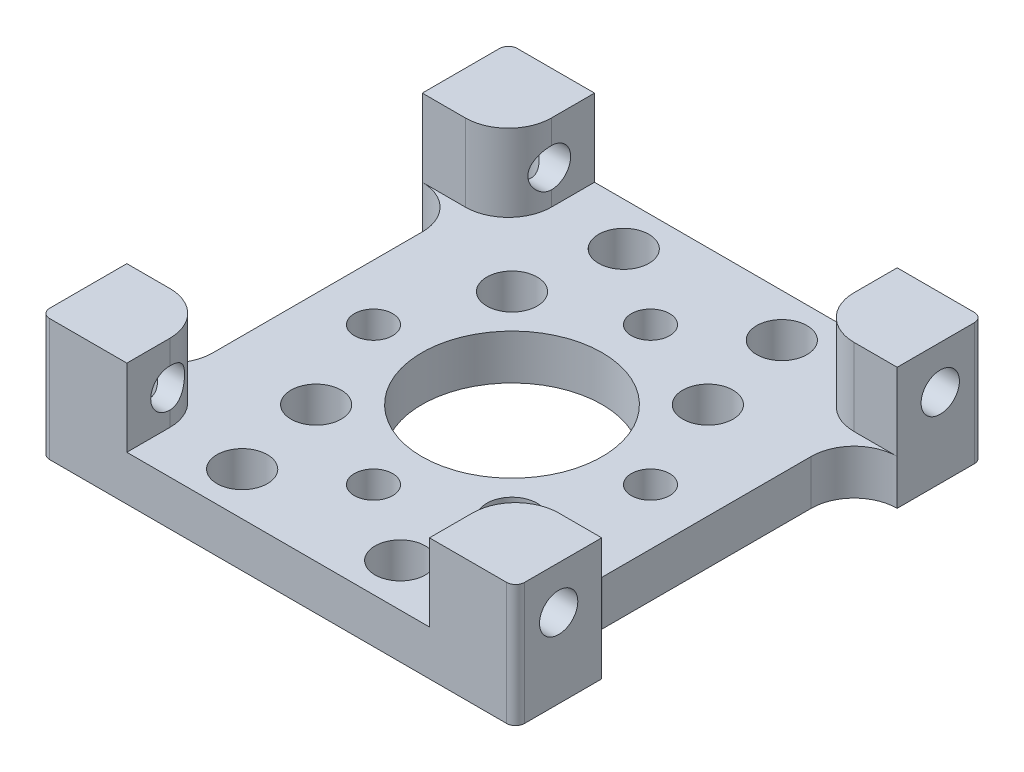
SolidWorks part; units mm, degrees
ref_plane "Front Plane" through (0, 0, 0) normal (0, 0, 1) x (1, 0, 0)
ref_plane "Top Plane" through (0, 0, 0) normal (0, 1, 0) x (1, 0, 0)
ref_plane "Right Plane" through (0, 0, 0) normal (1, 0, 0) x (0, 0, -1)
ref_plane "Plane1" through (0, 3.175, 0) normal (0, 1, 0) x (1, 0, 0)
sketch "Sketch1" plane through (0, 3.175, 0) normal (0, 1, 0) x (1, 0, 0)
  line L0 (16.764, -16.51) -> (16.764, 16.51)
  line L1 (16.764, 16.51) -> (-16.764, 16.51)
  line L2 (-16.764, 16.51) -> (-16.764, -16.51)
  line L3 (-16.764, -16.51) -> (16.764, -16.51)
extrude "Boss-Extrude1" add sketch "Sketch1" against normal blind 3.175
sketch "Sketch2" plane through (0, 0, 0) normal (0, -1, 0) x (1, 0, 0)
  line L0 (16.764, -10.4292) -> (16.764, 10.4292)
  line L1 (13.7287, 7.3889) -> (13.7287, -7.3889)
  arc A0 (16.764, 10.4292) -> (13.7287, 7.3889) centre (16.7691, 7.3889) ccw
  arc A1 (13.7287, -7.3889) -> (16.764, -10.4292) centre (16.7691, -7.3889) ccw
extrude "Cut-Extrude1" cut sketch "Sketch2" against normal through all
sketch "Sketch3" plane through (0, 0, 0) normal (0, -1, 0) x (1, 0, 0)
  line L0 (-16.764, 10.4292) -> (-16.764, -10.4292)
  line L1 (-13.7287, -7.3889) -> (-13.7287, 7.3889)
  arc A0 (-16.764, -10.4292) -> (-13.7287, -7.3889) centre (-16.7691, -7.3889) ccw
  arc A1 (-13.7287, 7.3889) -> (-16.764, 10.4292) centre (-16.7691, 7.3889) ccw
extrude "Cut-Extrude2" cut sketch "Sketch3" against normal through all
ref_plane "Plane2" through (0, 0, -16.51) normal (0, 0, -1) x (-1, 0, 0)
sketch "Sketch4" plane through (0, 0, -16.51) normal (0, 0, -1) x (-1, 0, 0)
  line L0 (10.6832, 3.175) -> (16.764, 3.175)
  line L1 (16.764, 3.175) -> (16.764, 8.6284)
  line L2 (16.764, 8.6284) -> (10.6832, 8.6284)
  line L3 (10.6832, 8.6284) -> (10.6832, 3.175)
extrude "Boss-Extrude2" add sketch "Sketch4" against normal blind 6.0808
sketch "Sketch5" plane through (0, 0, -16.51) normal (0, 0, -1) x (-1, 0, 0)
  line L0 (-16.764, 8.6284) -> (-16.764, 3.175)
  line L1 (-16.764, 3.175) -> (-10.6832, 3.175)
  line L2 (-10.6832, 3.175) -> (-10.6832, 8.6284)
  line L3 (-10.6832, 8.6284) -> (-16.764, 8.6284)
extrude "Boss-Extrude3" add sketch "Sketch5" against normal blind 6.0808
ref_plane "Plane3" through (0, 0, 16.51) normal (0, 0, 1) x (1, 0, 0)
sketch "Sketch6" plane through (0, 0, 16.51) normal (0, 0, 1) x (1, 0, 0)
  line L0 (10.6832, 3.175) -> (16.764, 3.175)
  line L1 (16.764, 3.175) -> (16.764, 8.6284)
  line L2 (16.764, 8.6284) -> (10.6832, 8.6284)
  line L3 (10.6832, 8.6284) -> (10.6832, 3.175)
extrude "Boss-Extrude4" add sketch "Sketch6" against normal blind 6.0808
sketch "Sketch7" plane through (0, 0, 16.51) normal (0, 0, 1) x (1, 0, 0)
  line L0 (-16.764, 8.6284) -> (-16.764, 3.175)
  line L1 (-16.764, 3.175) -> (-10.6832, 3.175)
  line L2 (-10.6832, 3.175) -> (-10.6832, 8.6284)
  line L3 (-10.6832, 8.6284) -> (-16.764, 8.6284)
extrude "Boss-Extrude5" add sketch "Sketch7" against normal blind 6.0808
hole_wizard "Hole1" positions "Sketch9" profile "Sketch8" legacy
sketch "Sketch9" plane through (0, 3.175, 0) normal (0, 1, 0) x (1, 0, 0)
  point P0 (0, 0)
sketch "Sketch8" plane through (0, 3.175, 0) normal (1, 0, 0) x (0, 0, 1)
  line L0 (0, 0) -> (0, 3.175)
  line L1 (0, 3.175) -> (6.3627, 3.175)
  line L2 (6.3627, 3.175) -> (6.3627, 0)
  line L3 (6.3627, 0) -> (0, 0)
  line L4 (0, 110) -> (0, -10) construction
  dimension "Diameter" = 12.7254
  dimension "Depth" = 3.175
hole_wizard "M2.5 Clearance Hole1" positions "Sketch11" profile "Sketch10" hole size "M2.5" standard "ANSI Metric"
sketch "Sketch11" plane through (0, 3.175, 0) normal (0, 1, 0) x (1, 0, 0)
  point P0 (0, 9.779)
  point P1 (-9.779, 0)
  point P2 (0, -9.779)
  point P3 (9.779, 0)
sketch "Sketch10" plane through (0, 3.175, -9.779) normal (1, 0, 0) x (0, 0, 1)
  line L0 (0, 0) -> (0, 3.175)
  line L1 (0, 3.175) -> (1.3525, 3.175)
  line L2 (1.3525, 3.175) -> (1.3525, 0)
  line L5 (1.3525, 0) -> (0, 0)
  line L11 (0, -6.35) -> (0, 107.95) construction
  dimension "Thru Hole Dia." = 2.7051
  dimension "Thru Hole Depth" = 3.175
hole_wizard "M3 Clearance Hole1" positions "Sketch13" profile "Sketch12" hole size "M3" standard "ANSI Metric"
sketch "Sketch13" plane through (0, 3.175, 0) normal (0, 1, 0) x (1, 0, 0)
  point P0 (-5.5796, -13.4704)
  point P1 (5.5796, -13.4704)
  point P2 (5.5796, 13.4704)
  point P3 (-5.5796, 13.4704)
  point P4 (6.9148, 6.9148)
  point P5 (-6.9148, 6.9148)
  point P6 (-6.9148, -6.9148)
  point P7 (6.9148, -6.9148)
sketch "Sketch12" plane through (-5.5796, 3.175, 13.4704) normal (1, 0, 0) x (0, 0, 1)
  line L0 (0, 0) -> (0, 3.175)
  line L1 (0, 3.175) -> (1.778, 3.175)
  line L2 (1.778, 3.175) -> (1.778, 0)
  line L5 (1.778, 0) -> (0, 0)
  line L11 (0, -6.35) -> (0, 107.95) construction
  dimension "Thru Hole Dia." = 3.556
  dimension "Thru Hole Depth" = 3.175
hole_wizard "M2.5 Clearance Hole2" positions "Sketch15" profile "Sketch14" hole size "M2.5" standard "ANSI Metric"
sketch "Sketch15" plane through (16.764, 0, 0) normal (1, 0, 0) x (0, 0, -1)
  point P0 (-13.4704, 5.588)
sketch "Sketch14" plane through (16.764, 5.588, 13.4704) normal (0, 1, 0) x (0, 0, -1)
  line L0 (0, 0) -> (0, 39.6088)
  line L1 (0, 39.6088) -> (1.3525, 39.6088)
  line L2 (1.3525, 39.6088) -> (1.3525, 0)
  line L5 (1.3525, 0) -> (0, 0)
  line L10 (0, 39.6088) -> (-1.3525, 39.6088) construction
  line L11 (0, -6.35) -> (0, 107.95) construction
  dimension "Hole Dia." = 2.7051
  dimension "Hole Depth" = 39.6088
  dimension "Drill Angle" = 180
hole_wizard "M2.5 Clearance Hole3" positions "Sketch17" profile "Sketch16" hole size "M2.5" standard "ANSI Metric"
sketch "Sketch17" plane through (-16.764, 0, 0) normal (-1, 0, 0) x (0, 0, 1)
  point P0 (-13.4704, 5.588)
sketch "Sketch16" plane through (-16.764, 5.588, -13.4704) normal (0, 1, 0) x (0, 0, 1)
  line L0 (0, 0) -> (0, 39.6088)
  line L1 (0, 39.6088) -> (1.3525, 39.6088)
  line L2 (1.3525, 39.6088) -> (1.3525, 0)
  line L5 (1.3525, 0) -> (0, 0)
  line L10 (0, 39.6088) -> (-1.3525, 39.6088) construction
  line L11 (0, -6.35) -> (0, 107.95) construction
  dimension "Hole Dia." = 2.7051
  dimension "Hole Depth" = 39.6088
  dimension "Drill Angle" = 180
hole_wizard "M2.5 Clearance Hole4" positions "Sketch19" profile "Sketch18" hole size "M2.5" standard "ANSI Metric"
sketch "Sketch19" plane through (0, 0, 0) normal (0, -1, 0) x (-1, 0, 0)
  point P0 (13.4704, 13.4704)
  point P1 (-13.4704, 13.4704)
  point P2 (-13.4704, -13.4704)
  point P3 (13.4704, -13.4704)
sketch "Sketch18" plane through (-13.4704, 0, -13.4704) normal (1, 0, 0) x (0, 0, -1)
  line L0 (0, 0) -> (0, 4.2355)
  line L1 (0, 4.2355) -> (1.3525, 4.2355)
  line L2 (1.3525, 4.2355) -> (1.3525, 0)
  line L5 (1.3525, 0) -> (0, 0)
  line L11 (0, -6.35) -> (0, 107.95) construction
  dimension "Thru Hole Dia." = 2.7051
  dimension "Thru Hole Depth" = 4.2355
fillet "Fillet1" radius 0.635 4 edges at (-16.764, 4.3142, -16.51) (-16.764, 4.3142, 16.51) (16.764, 4.3142, 16.51) (16.764, 4.3142, -16.51) tangent propagation no
fillet "Fillet2" radius 3.0404 4 edges at (-10.6832, 5.9017, -10.4292) (10.6832, 5.9017, -10.4292) (10.6832, 5.9017, 10.4292) (-10.6832, 5.9017, 10.4292) tangent propagation no
